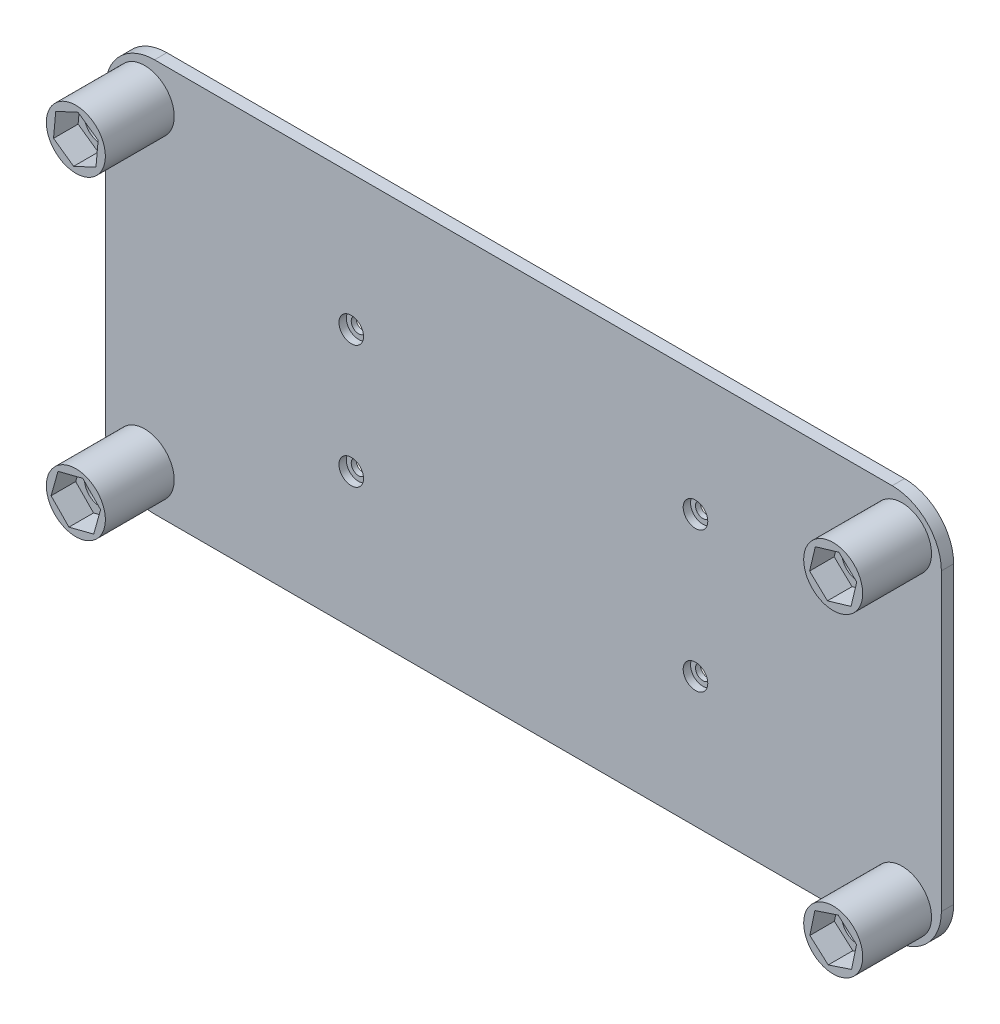
SolidWorks part; units mm, degrees
ref_plane "前视基准面" through (0, 0, 0) normal (0, 0, 1) x (1, 0, 0)
ref_plane "上视基准面" through (0, 0, 0) normal (0, 1, 0) x (1, 0, 0)
ref_plane "右视基准面" through (0, 0, 0) normal (1, 0, 0) x (0, 0, -1)
sketch "草图1" plane through (0, 0, 0) normal (0, 0, 1) x (1, 0, 0)
  line L1 (-72.5741, 35.4874) -> (77.4259, 35.4874)
  line L2 (-82.5741, 25.4874) -> (-82.5741, -34.5126)
  line L3 (-72.5741, -44.5126) -> (77.4259, -44.5126)
  line L4 (87.4259, 25.4874) -> (87.4259, -34.5126)
  arc A0 (-72.5741, 35.4874) -> (-82.5741, 25.4874) centre (-72.5741, 25.4874) ccw
  arc A1 (-72.5741, -44.5126) -> (-82.5741, -34.5126) centre (-72.5741, -34.5126) cw
  arc A2 (87.4259, 25.4874) -> (77.4259, 35.4874) centre (77.4259, 25.4874) ccw
  arc A3 (87.4259, -34.5126) -> (77.4259, -44.5126) centre (77.4259, -34.5126) cw
  dimension "D1" = 10
  dimension "D2" = 10
  dimension "D3" = 10
  dimension "D4" = 10
  dimension "D5" = 80
  dimension "D6" = 170
extrude "凸台-拉伸1" add sketch "草图1" along normal blind 2.5
ref_plane "for screw hole" through (0, 0, 2.5) normal (0, 0, 1) x (1, 0, 0)
sketch "草图2" plane through (0, 0, 2.5) normal (0, 0, 1) x (1, 0, 0)
  line L0 (77.4259, 35.4874) -> (-72.5741, 35.4874) construction
  line L1 (-82.5741, 25.4874) -> (-82.5741, -34.5126) construction
  circle A0 centre (-32.5741, 7.9874) radius 1.5
  circle A1 centre (-32.5741, -17.0126) radius 1.5
  circle A2 centre (37.4259, 10.4502) radius 1.5
  circle A3 centre (37.4259, -18.0901) radius 1.5
  dimension "D2" = 3
  dimension "D3" = 3
  dimension "D4" = 3
  dimension "D8" = 27.5
  dimension "D9" = 50
  dimension "D10" = 50
  dimension "D11" = 3
  dimension "D5" = 70
  dimension "D6" = 70
  dimension "D7" = 25
extrude "切除-拉伸1" cut sketch "草图2" against normal blind 10 and the other way blind 42
ref_plane "for outer screw hole" through (0, 0, 2.5) normal (0, 0, 1) x (1, 0, 0)
sketch "草图3" plane through (0, 0, 2.5) normal (0, 0, 1) x (1, 0, 0)
  circle A0 centre (-32.5741, 7.9874) radius 2.5
  circle A1 centre (37.4259, 10.4502) radius 2.5
  circle A2 centre (37.4259, -18.0901) radius 2.5
  circle A3 centre (-32.5741, -17.0126) radius 2.5
  dimension "D1" = 5
  dimension "D2" = 5
  dimension "D3" = 5
  dimension "D4" = 5
extrude "切除-拉伸2" cut sketch "草图3" against normal blind 1.5
ref_plane "for stands" through (0, 0, 2.5) normal (0, 0, 1) x (1, 0, 0)
sketch "草图7" plane through (0, 0, 2.5) normal (0, 0, 1) x (1, 0, 0)
  line L0 (77.4259, 35.4874) -> (-72.5741, 35.4874) construction
  line L1 (-82.5741, 25.4874) -> (-82.5741, -34.5126) construction
  line L2 (-72.5741, -44.5126) -> (77.4259, -44.5126) construction
  line L3 (87.4259, -34.5126) -> (87.4259, 25.4874) construction
  circle A0 centre (-74.5741, 27.4874) radius 6
  circle A1 centre (-74.5741, -36.5126) radius 6
  circle A2 centre (79.4259, 27.4874) radius 6
  circle A3 centre (79.4259, -36.5126) radius 6
  point P12 (79.4259, -30.5126)
  point P14 (79.4259, 21.4874)
  dimension "D1" = 12
  dimension "D2" = 12
  dimension "D3" = 12
  dimension "D4" = 12
  dimension "D7" = 8
  dimension "D5" = 8
  dimension "D6" = 8
  dimension "D8" = 8
  dimension "D9" = 8
  dimension "D10" = 8
  dimension "D11" = 8
  dimension "D12" = 8
extrude "凸台-拉伸4" add sketch "草图7" along normal blind 14
ref_plane "button left hole" through (0, 0, 16.5) normal (0, 0, 1) x (1, 0, 0)
ref_plane "up left hole" through (0, 0, 16.5) normal (0, 0, 1) x (1, 0, 0)
ref_plane "up right hole" through (0, 0, 16.5) normal (0, 0, 1) x (1, 0, 0)
ref_plane "button right hole" through (0, 0, 16.5) normal (0, 0, 1) x (1, 0, 0)
sketch "草图9" plane through (0, 0, 16.5) normal (0, 0, 1) x (1, 0, 0)
  line L1 (-70.9446, -40.2262) -> (-69.5433, -35.2262)
  line L2 (-69.5433, -35.2262) -> (-73.1728, -31.5126)
  line L3 (-73.1728, -31.5126) -> (-78.2036, -32.7991)
  line L4 (-78.2036, -32.7991) -> (-79.6049, -37.7991)
  line L5 (-79.6049, -37.7991) -> (-75.9754, -41.5126)
  line L6 (-75.9754, -41.5126) -> (-70.9446, -40.2262)
  circle A0 centre (-74.5741, -36.5126) radius 4.497 construction
  circle A1 centre (-74.5741, -36.5126) radius 6 construction
  dimension "D1" = 5
  dimension "D2" = 0
extrude "button left nut " cut sketch "草图9" against normal blind 5
sketch "草图10" plane through (0, 0, 16.5) normal (0, 0, 1) x (1, 0, 0)
  line L1 (-70.4846, 24.6106) -> (-70.038, 29.5906)
  line L2 (-70.038, 29.5906) -> (-74.1275, 32.4674)
  line L3 (-74.1275, 32.4674) -> (-78.6636, 30.3642)
  line L4 (-78.6636, 30.3642) -> (-79.1102, 25.3842)
  line L5 (-79.1102, 25.3842) -> (-75.0207, 22.5074)
  line L6 (-75.0207, 22.5074) -> (-70.4846, 24.6106)
  circle A0 centre (-74.5741, 27.4874) radius 4.3301 construction
  circle A1 centre (-74.5741, 27.4874) radius 6 construction
  dimension "D1" = 5
  dimension "D2" = 0
extrude "up left nut" cut sketch "草图10" against normal blind 5
sketch "草图11" plane through (0, 0, 16.5) normal (0, 0, 1) x (1, 0, 0)
  line L1 (83.0542, 24.0471) -> (84.2194, 28.9094)
  line L2 (84.2194, 28.9094) -> (80.5911, 32.3497)
  line L3 (80.5911, 32.3497) -> (75.7976, 30.9277)
  line L4 (75.7976, 30.9277) -> (74.6324, 26.0653)
  line L5 (74.6324, 26.0653) -> (78.2607, 22.6251)
  line L6 (78.2607, 22.6251) -> (83.0542, 24.0471)
  circle A0 centre (79.4259, 27.4874) radius 4.3301 construction
  circle A2 centre (79.4259, 27.4874) radius 6 construction
  dimension "D2" = 0
  dimension "D1" = 5
extrude "up right nut" cut sketch "草图11" against normal blind 5
sketch "草图12" plane through (0, 0, 16.5) normal (0, 0, 1) x (1, 0, 0)
  line L1 (83.1629, -39.8344) -> (84.1712, -34.9371)
  line L2 (84.1712, -34.9371) -> (80.4341, -31.6153)
  line L3 (80.4341, -31.6153) -> (75.6888, -33.1908)
  line L4 (75.6888, -33.1908) -> (74.6806, -38.0881)
  line L5 (74.6806, -38.0881) -> (78.4176, -41.4099)
  line L6 (78.4176, -41.4099) -> (83.1629, -39.8344)
  circle A0 centre (79.4259, -36.5126) radius 4.3301 construction
  circle A1 centre (79.4259, -36.5126) radius 6 construction
  dimension "D2" = 0
  dimension "D1" = 5
extrude "button right nut" cut sketch "草图12" against normal blind 5
ref_plane "基准面13" through (0, 0, 16.5) normal (0, 0, 1) x (1, 0, 0)
ref_plane "基准面14" through (0, 0, 16.5) normal (0, 0, 1) x (1, 0, 0)
ref_plane "基准面15" through (0, 0, 16.5) normal (0, 0, 1) x (1, 0, 0)
ref_plane "基准面16" through (0, 0, 16.5) normal (0, 0, 1) x (1, 0, 0)
sketch "草图13" plane through (0, 0, 16.5) normal (0, 0, 1) x (1, 0, 0)
  circle A0 centre (-74.5741, -36.5126) radius 3.25
  dimension "D1" = 6.5
extrude "切除-拉伸7" cut sketch "草图13" against normal blind 13
sketch "草图15" plane through (0, 0, 16.5) normal (0, 0, 1) x (1, 0, 0)
  circle A0 centre (-74.5741, 27.4874) radius 3.25
  circle A1 centre (-74.5741, 27.4874) radius 6 construction
  dimension "D1" = 6.5
  dimension "D2" = 0
extrude "切除-拉伸8" cut sketch "草图15" against normal blind 13
sketch "草图16" plane through (0, 0, 16.5) normal (0, 0, 1) x (1, 0, 0)
  circle A0 centre (79.4259, 27.4874) radius 3.25
  dimension "D1" = 6.5
extrude "切除-拉伸9" cut sketch "草图16" against normal blind 13
sketch "草图17" plane through (0, 0, 16.5) normal (0, 0, 1) x (1, 0, 0)
  circle A0 centre (79.4259, -36.5126) radius 3.25
  circle A1 centre (79.4259, -36.5126) radius 6 construction
  point P4 (79.4259, -36.2982)
  point P5 (79.4259, -36.2982)
  point P6 (79.4259, -36.2982)
  point P7 (79.4259, -36.2982)
  dimension "D1" = 6.5
  dimension "D2" = 0
extrude "切除-拉伸10" cut sketch "草图17" against normal blind 13
